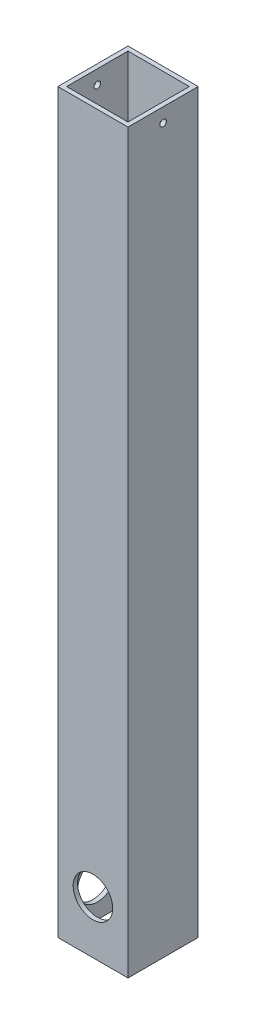
SolidWorks part; units mm, degrees
material "6063-T1"
ref_plane "Front Plane" through (0, 0, 0) normal (0, 0, 1) x (1, 0, 0)
ref_plane "Top Plane" through (0, 0, 0) normal (0, 1, 0) x (1, 0, 0)
ref_plane "Right Plane" through (0, 0, 0) normal (1, 0, 0) x (0, 0, -1)
sketch "Sketch1" plane through (0, 0, 0) normal (0, 1, 0) x (1, 0, 0)
  line L1 (-25.4, 25.4) -> (25.4, 25.4)
  line L2 (-25.4, 25.4) -> (-25.4, -25.4)
  line L3 (-25.4, -25.4) -> (25.4, -25.4)
  line L4 (25.4, 25.4) -> (25.4, -25.4)
  line L5 (-25.4, 25.4) -> (25.4, -25.4) construction
  line L6 (-25.4, -25.4) -> (25.4, 25.4) construction
  line L7 (-22.225, -22.225) -> (22.225, -22.225)
  line L8 (-22.225, -22.225) -> (-22.225, 22.225)
  line L9 (-22.225, 22.225) -> (22.225, 22.225)
  line L10 (22.225, -22.225) -> (22.225, 22.225)
  line L11 (-22.225, -22.225) -> (22.225, 22.225) construction
  line L12 (-22.225, 22.225) -> (22.225, -22.225) construction
  point P0 (0, 0)
  point P6 (0, 0)
  dimension "D1" = 50.8
  dimension "D2" = 50.8
  dimension "D3" = 3.175
  dimension "D4" = 3.175
extrude "Boss-Extrude1" add sketch "Sketch1" along normal blind 533.4
sketch "Sketch2" plane through (-25.4, 0, 0) normal (-1, 0, 0) x (0, 0, 1)
  line L0 (-25.4, 0) -> (25.4, 0) construction
  circle A0 centre (0, 25.4) radius 14.2875
  dimension "D1" = 28.575
  dimension "D2" = 25.4
extrude "Cut-Extrude1" cut sketch "Sketch2" against normal blind 3.175
sketch "Sketch3" plane through (0, 0, -25.4) normal (0, 0, -1) x (-1, 0, 0)
  line L0 (-25.4, 0) -> (25.4, 0) construction
  circle A0 centre (0, 38.1) radius 14.3002
  dimension "D1" = 28.6004
  dimension "D2" = 38.1
extrude "Cut-Extrude2" cut sketch "Sketch3" against normal through all
sketch "Sketch4" plane through (-25.4, 0, 0) normal (-1, 0, 0) x (0, 0, 1)
  line L0 (25.4, 533.4) -> (25.4, 0) construction
  line L1 (-25.4, 533.4) -> (25.4, 533.4) construction
  circle A0 centre (0, 523.24) radius 2.3813
  dimension "D1" = 4.7625
  dimension "D2" = 25.4
  dimension "D3" = 10.16
extrude "Cut-Extrude3" cut sketch "Sketch4" against normal through all
